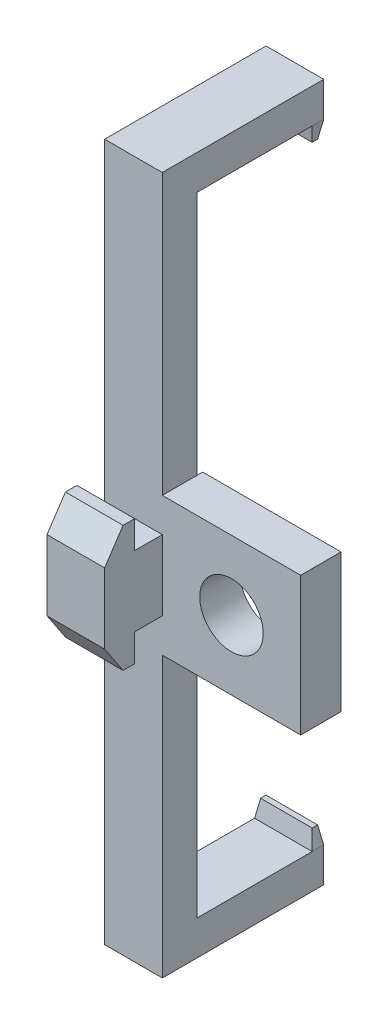
SolidWorks part; units mm, degrees
note: '?' marks a value the reader was unsure of. The reader was unsure of these and kept them because the rebuilt part matched: shared geometry of "Sketch1<5>".
ref_plane "Front Plane" through (0, 0, 0) normal (0, 0, 1) x (1, 0, 0)
ref_plane "Top Plane" through (0, 0, 0) normal (0, 1, 0) x (1, 0, 0)
ref_plane "Right Plane" through (0, 0, 0) normal (1, 0, 0) x (0, 0, -1)
sketch "Sketch1" plane through (0, 0, 0) normal (0, 0, 1) x (1, 0, 0)
  line L0 (-82.5, 0) -> (-85.5, 0)
  line L1 (-82.5, -27.25) -> (82.5, -27.25) construction
  line L2 (-82.5, -27.25) -> (-82.5, 27.25) construction
  line L3 (-82.5, 27.25) -> (82.5, 27.25) construction
  line L4 (82.5, -27.25) -> (82.5, 27.25) construction
  line L5 (-82.5, -27.25) -> (82.5, 27.25) construction
  line L6 (-82.5, 27.25) -> (82.5, -27.25) construction
  line L7 (-85.5, 30.25) -> (85.5, 30.25) construction
  line L8 (-85.5, 30.25) -> (-85.5, -30.25) construction
  line L9 (-85.5, -30.25) -> (85.5, -30.25) construction
  line L10 (85.5, 30.25) -> (85.5, -30.25) construction
  line L11 (-85.5, 30.25) -> (85.5, -30.25) construction
  line L12 (-85.5, -30.25) -> (85.5, 30.25) construction
  line L13 (0, 27.25) -> (0, 30.25) construction
  line L19 (-80.5114, -27.25) -> (-75.5114, -27.25)
  line L20 (-80.5114, -27.25) -> (-80.5114, -30.25)
  line L21 (-80.5114, -30.25) -> (-75.5114, -30.25)
  line L22 (-75.5114, -27.25) -> (-75.5114, -30.25)
  line L23 (-75.5114, -27.25) -> (-80.5114, -27.25)
  line L24 (-75.5114, -27.25) -> (-75.5114, 27.25)
  line L25 (-75.5114, 27.25) -> (-80.5114, 27.25)
  line L26 (-80.5114, -27.25) -> (-80.5114, 27.25)
  line L27 (-75.5114, 30.25) -> (-80.5114, 30.25)
  line L28 (-75.5114, 30.25) -> (-75.5114, 27.25)
  line L29 (-75.5114, 27.25) -> (-80.5114, 27.25)
  line L30 (-80.5114, 30.25) -> (-80.5114, 27.25)
  point P0 (0, 0)
  point P6 (0, 0)
  dimension "D1" = 54.5
  dimension "D2" = 165
  dimension "D3" = 3
  dimension "D4" = 5
extrude "Boss-Extrude3" add sketch "Sketch1" along normal blind 3 contours L26 L19 L24 L25 | L22 L19 L20 L21 | L27 L30 L25 L28
extrude "Boss-Extrude4" add sketch "Sketch1<5>" against normal blind 11 contours L22 L19 L20 L21 | L27 L30 L25 L28
sketch "Sketch1<5>" plane through (0, 0, 0) normal (0, 0, 1) x (1, 0, 0) same geometry as "Sketch1"
ref_plane "Plane2" through (0, 0, 0) normal (0, 1, 0) x (1, 0, 0)
sketch "Sketch3" plane through (0, -27.25, 0) normal (0, 1, 0) x (1, 0, 0)
  line L0 (-80.5114, 11) -> (-75.5114, 11) construction
  line L1 (-80.5114, 11) -> (-75.5114, 11)
  line L2 (-80.5114, 11) -> (-80.5114, 10)
  line L3 (-80.5114, 10) -> (-75.5114, 10)
  line L4 (-75.5114, 11) -> (-75.5114, 10)
  line L5 (-80.5114, 11) -> (-80.5114, 0) construction
  line L6 (-75.5114, 11) -> (-75.5114, 0) construction
  dimension "D1" = 1
extrude "Boss-Extrude5" add sketch "Sketch3" along normal blind 1.5 draft 10
mirror "Mirror1" about plane through (0, 0, 0) normal (0, 1, 0) of "Boss-Extrude5"
sketch "Sketch5" plane through (-75.5114, 0, 0) normal (1, 0, 0) x (0, 0, -1)
  line L0 (-3, -30.25) -> (-3, 30.25) construction
  point P0 (0, 0)
  line B0 (-3, 9.5) -> (-2, 9.5)
  line B1 (-3, 3.05) -> (-5.4, 3.05)
  line B2 (-3, -3.05) -> (-5.4, -3.05)
  line B3 (-5.4, 3.05) -> (-5.4, 5.45)
  line B4 (-5.4, 5.45) -> (-6.4, 5.45)
  line B5 (-5.4, -3.05) -> (-5.4, -5.45)
  line B6 (-5.4, -5.45) -> (-6.4, -5.45)
  line B7 (-3, 3.05) -> (-3, 9.5)
  line B8 (-2, 9.5) -> (-2, -9.5)
  line B9 (-3, -3.05) -> (-3, -9.5)
  line B10 (-2, -9.5) -> (-3, -9.5)
  line B11 (-6.4, 5.45) -> (-8, 3.05)
  line B12 (-6.4, -5.45) -> (-8, -3.05)
  line B13 (-8, -3.05) -> (-8, 3.05)
sketch_block_instance "Block-2020 rail insert-1"
sketch_block "Block1" parameters "D1"=5, "D2"=6.1, "D3"=2.4, "D4"=2.4, "D5"=1, "D6"=1, "D7"=19
extrude "Boss-Extrude6" add sketch "Sketch5" against normal up to surface (5 mm away) up to face at (-80.5114, 0, -5.8)
sketch "Sketch34" plane through (-75.5114, -10.7014, -2.5234) normal (1, 0, 0) x (0, 0, -1)
  line L0 (-5.5234, -19.5486) -> (-5.5234, 7.6514) construction
  line L6 (-2.5234, 14.9527) -> (-2.5234, 6.45) construction
  line L7 (-2.5234, 10.7014) -> (-3.7734, 10.7014) construction
  line L8 (-2.5234, 10.7014) -> (-4.9955, 10.7014) construction
  line L9 (-5.5234, 16.7014) -> (-2.0234, 16.7014)
  line L10 (-5.5234, 16.7014) -> (-5.5234, 4.7014)
  line L11 (-5.5234, 4.7014) -> (-2.0234, 4.7014)
  line L12 (-2.0234, 16.7014) -> (-2.0234, 4.7014)
  line L13 (-5.5234, 16.7014) -> (-2.0234, 4.7014) construction
  line L14 (-5.5234, 4.7014) -> (-2.0234, 16.7014) construction
  line L15 (-2.5234, -16.5486) -> (-2.5234, 37.9514) construction
  point P10 (0, 0)
  dimension "D1" = 12
  dimension "D2" = 3.5
extrude "Boss-Extrude2" add sketch "Sketch34" along normal blind 12
sketch "Sketch4" plane through (-75.5114, -10.7014, 3) normal (0, 0, 1) x (1, 0, 0)
  line L0 (6, 10.7014) -> (12, 10.7014) construction
  line L1 (12, 16.7014) -> (12, 4.7014) construction
  line L2 (6, 10.7014) -> (6, 4.7014) construction
  line L3 (12, 4.7014) -> (0, 4.7014) construction
  circle A0 centre (6, 10.7014) radius 2.75
  dimension "D1" = 5.5
extrude "Cut-Extrude2" cut sketch "Sketch4" against normal up to next contours A0
other "m5 mount hole<1>"
sketch "Sketch35" plane through (-80.5114, 0, 0) normal (-1, 0, 0) x (0, 0, 1)
  line L0 (3, -3.05) -> (3, 3.05) construction
  point P4 (3, 0)
ref_axis "Axis1" through (-80.5114, 0, 3) along (-1, 0, 0)?
